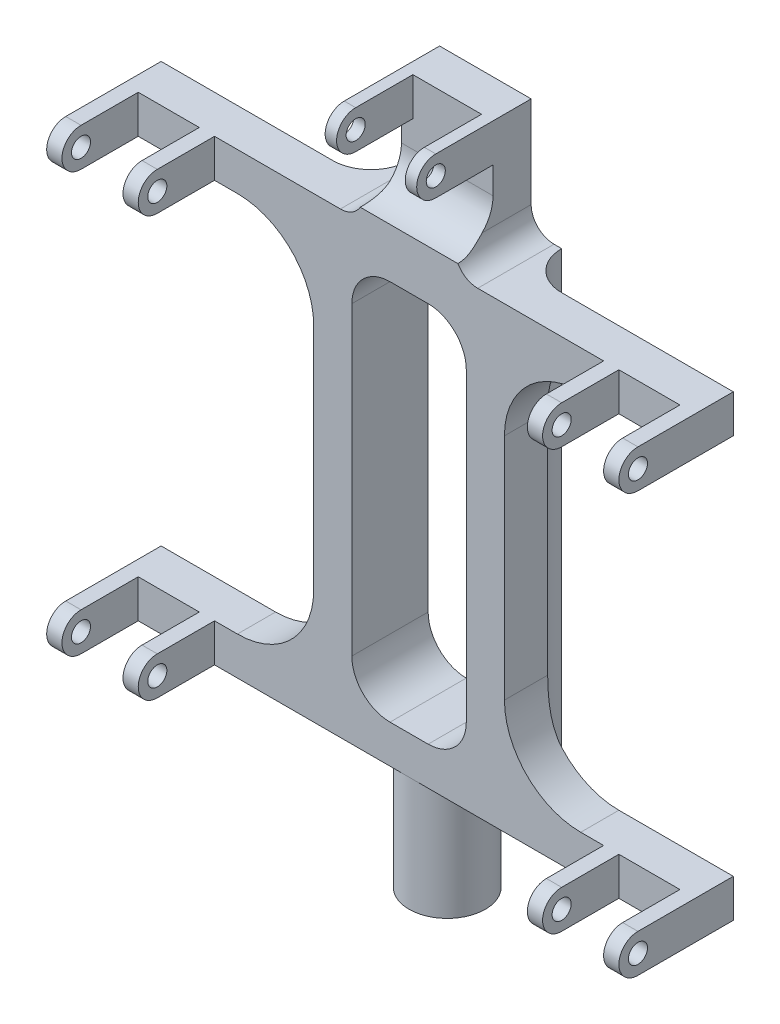
SolidWorks part; units mm, degrees
material "Plain Carbon Steel"
ref_plane "Front Plane" through (0, 0, 0) normal (0, 0, 1) x (1, 0, 0)
ref_plane "Top Plane" through (0, 0, 0) normal (0, 1, 0) x (1, 0, 0)
ref_plane "Right Plane" through (0, 0, 0) normal (1, 0, 0) x (0, 0, -1)
sketch "Sketch1" plane through (0, 0, 0) normal (0, 1, 0) x (1, 0, 0)
  line L1 (-75, -10) -> (75, -10)
  line L2 (-75, -10) -> (-75, 10)
  line L3 (-75, 10) -> (75, 10)
  line L4 (75, -10) -> (75, 10)
  line L5 (-75, -10) -> (75, 10) construction
  line L6 (-75, 10) -> (75, -10) construction
  circle A0 centre (0, 0) radius 10
  point P0 (0, 0)
  dimension "D1" = 150
  dimension "D2" = 20
extrude "Boss-Extrude1" add sketch "Sketch1" along normal blind 120 contours A0 L3 L2 L1 | A0 L1 L4 L3 | A0 region at (-41.3899, 0, 0) region at (41.3899, 0, 0) region at (0, 0, 0)
extrude "Boss-Extrude2" add sketch "Sketch1<3>" against normal blind 30 contours A0
sketch "Sketch1<3>" plane through (0, 0, 0) normal (0, 1, 0) x (1, 0, 0) same geometry as "Sketch1"
sketch "Sketch2" plane through (-75, 0, 0) normal (-1, 0, 0) x (0, 0, 1)
  line L0 (10, 120) -> (10, 110)
  line L1 (10, 120) -> (10, 0) construction
  line L2 (10, 110) -> (25, 110)
  line L3 (25, 120) -> (10, 120)
  arc A0 (25, 110) -> (25, 120) centre (25, 115) ccw
  circle A1 centre (25, 115) radius 2.5
  dimension "D1" = 5
  dimension "D2" = 5
  dimension "D3" = 15
extrude "Boss-Extrude3" add sketch "Sketch2" against normal blind 4
pattern_linear "LPattern1" count 2 spacing 20 along (1, 0, 0) of "Boss-Extrude3"
mirror "Mirror1" about plane through (0, 0, 0) normal (1, 0, 0) of "LPattern1"
ref_plane "Plane1" through (0, 60, 0) normal (0, 1, 0) x (1, 0, 0)
mirror "Mirror2" about plane through (0, 60, 0) normal (0, 1, 0) of "Mirror1", "LPattern1"
sketch "Sketch5" plane through (0, 120, 0) normal (0, 1, 0) x (1, 0, 0)
  line L0 (-75, 0) -> (-30, 0)
  line L1 (-75, -25) -> (-75, 10) construction
  line L2 (-75, 10) -> (75, 10) construction
  line L3 (-75, 0) -> (-75, 10)
  line L4 (-75, 10) -> (-20, 10)
  line L5 (0, 10) -> (0, -10) construction
  line L6 (-51, -10) -> (51, -10) construction
  line L7 (75, 10) -> (20, 10)
  line L8 (75, 0) -> (30, 0)
  line L9 (75, 0) -> (75, 10)
  arc A0 (-30, 0) -> (-20, 10) centre (-30, 10) ccw
  arc A1 (30, 0) -> (20, 10) centre (30, 10) cw
  dimension "D1" = 45
extrude "Cut-Extrude2" cut sketch "Sketch5" against normal through all
sketch "Sketch6" plane through (0, 120, 0) normal (0, 1, 0) x (1, 0, 0)
  line L0 (-30, 0) -> (-30, -10)
  line L1 (-51, -10) -> (51, -10) construction
  line L2 (-30, -10) -> (30, -10)
  line L3 (30, -10) -> (30, 0)
  line L18 (20, 10) -> (-20, 10)
  line L20 (-75, 0) -> (-75, -25)
  line L21 (-75, -25) -> (-71, -25)
  line L22 (-71, -25) -> (-71, -10)
  line L23 (-71, -10) -> (-55, -10)
  line L24 (-55, -10) -> (-55, -25)
  line L25 (-55, -25) -> (-51, -25)
  line L26 (-51, -25) -> (-51, -10)
  line L27 (-51, -10) -> (51, -10)
  line L28 (51, -10) -> (51, -25)
  line L29 (51, -25) -> (55, -25)
  line L30 (55, -25) -> (55, -10)
  line L31 (55, -10) -> (71, -10)
  line L32 (71, -10) -> (71, -25)
  line L33 (71, -25) -> (75, -25)
  line L34 (75, -25) -> (75, 0)
  line L36 (20, 10) -> (-20, 10)
  line L39 (-30, 0) -> (-75, 0)
  line L40 (75, 0) -> (30, 0)
  arc A2 (20, 10) -> (30, 0) centre (30, 10) ccw
  arc A3 (20, 10) -> (30, 0) centre (30, 10) ccw
  arc A4 (-30, 0) -> (-20, 10) centre (-30, 10) ccw
  arc A5 (-30, 0) -> (-20, 10) centre (-30, 10) ccw
  dimension "D1" = 0
extrude "Boss-Extrude4" add sketch "Sketch6" along normal blind 30
sketch "Sketch3" plane through (0, 0, 10) normal (0, 0, 1) x (1, 0, 0)
  line L0 (-75, 10) -> (-45, 10)
  line L1 (0, 120) -> (0, 0) construction
  line L3 (-75, 60) -> (75, 60) construction
  line L4 (-75, 110) -> (-75, 10) construction
  line L5 (75, 110) -> (75, 10) construction
  line L6 (-25, 30) -> (-25, 90)
  line L7 (-75, 110) -> (-45, 110)
  line L8 (75, 10) -> (45, 10)
  line L9 (25, 30) -> (25, 90)
  line L10 (75, 110) -> (45, 110)
  line L11 (-75, 110) -> (-75, 10)
  line L12 (75, 110) -> (75, 10)
  line L13 (30, 120) -> (51, 120) construction
  line L14 (-5, 10) -> (5, 10)
  line L15 (-15, 20) -> (-15, 100)
  line L16 (-5, 110) -> (5, 110)
  line L17 (15, 20) -> (15, 100)
  line L18 (-15, 10) -> (15, 110) construction
  line L19 (-15, 110) -> (15, 10) construction
  line L20 (-30, 120) -> (-18, 120)
  line L21 (-12, 126) -> (-12, 150)
  line L22 (-30, 150) -> (30, 150) construction
  line L23 (-12, 150) -> (-30, 150)
  line L24 (-30, 150) -> (-30, 120)
  line L26 (30, 150) -> (30, 120)
  line L27 (30, 120) -> (18, 120)
  line L28 (12, 126) -> (12, 150)
  line L29 (12, 150) -> (30, 150)
  arc A0 (-45, 10) -> (-25, 30) centre (-45, 30) ccw
  arc A1 (-45, 110) -> (-25, 90) centre (-45, 90) cw
  arc A2 (45, 10) -> (25, 30) centre (45, 30) cw
  arc A3 (45, 110) -> (25, 90) centre (45, 90) ccw
  arc A4 (-5, 10) -> (-15, 20) centre (-5, 20) cw
  arc A5 (5, 10) -> (15, 20) centre (5, 20) ccw
  arc A6 (5, 110) -> (15, 100) centre (5, 100) cw
  arc A7 (-15, 100) -> (-5, 110) centre (-5, 100) cw
  arc A8 (-18, 120) -> (-12, 126) centre (-18, 126) ccw
  arc A9 (18, 120) -> (12, 126) centre (18, 126) cw
  point P22 (-25, 60)
  point P30 (0, 60)
  dimension "D2" = 20
  dimension "D5" = 10
  dimension "D1" = 25
  dimension "D3" = 100
  dimension "D4" = 30
  dimension "D6" = 24
  dimension "D7" = 12
extrude "Cut-Extrude1" cut sketch "Sketch3" against normal through all
sketch "Sketch7" plane through (0, 0, 0) normal (1, 0, 0) x (0, 0, -1)
  line L0 (-10, 150) -> (0, 150)
  line L1 (10, 150) -> (-10, 150) construction
  line L2 (0, 150) -> (0, 133)
  line L3 (-10, 126) -> (-10, 120) construction
  line L4 (-10, 150) -> (-10, 126) construction
  line L5 (-10, 150) -> (-10, 123)
  arc A0 (0, 133) -> (-10, 123) centre (-10, 133) cw
extrude "Cut-Extrude3" cut sketch "Sketch7" against normal blind 30 and the other way blind 30
sketch "Sketch8" plane through (-12, 0, 0) normal (-1, 0, 0) x (0, 0, 1)
  line L0 (0, 150) -> (0, 140)
  line L2 (0, 140) -> (15, 140)
  line L3 (15, 150) -> (0, 150)
  line L4 (0, 150) -> (0, 133) construction
  arc A0 (15, 140) -> (15, 150) centre (15, 145) ccw
  circle A1 centre (15, 145) radius 2.5
  dimension "D1" = 5
  dimension "D2" = 5
  dimension "D3" = 15
extrude "Boss-Extrude5" add sketch "Sketch8" against normal blind 3
mirror "Mirror5" about plane through (0, 0, 0) normal (1, 0, 0) of "Boss-Extrude5"
